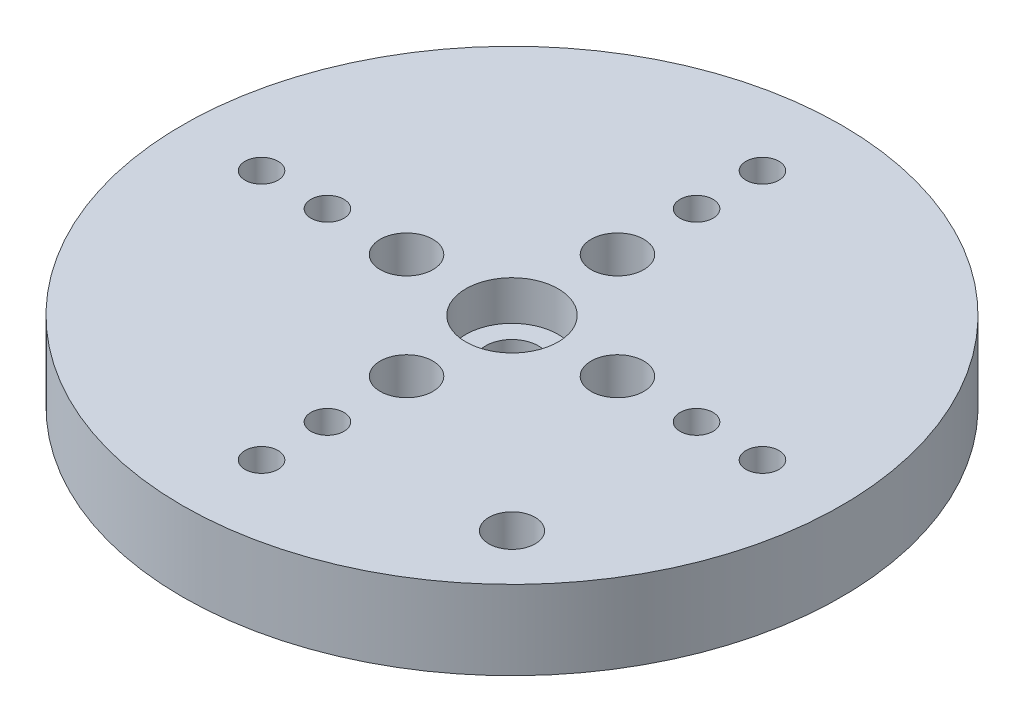
SolidWorks part; units mm, degrees
ref_plane "Front Plane" through (0, 0, 0) normal (0, 0, 1) x (1, 0, 0)
ref_plane "Top Plane" through (0, 0, 0) normal (0, 1, 0) x (1, 0, 0)
ref_plane "Right Plane" through (0, 0, 0) normal (1, 0, 0) x (0, 0, -1)
sketch "Sketch1" plane through (0, 0, 0) normal (0, 1, 0) x (1, 0, 0)
  circle A0 centre (0, 0) radius 25
  dimension "D1" = 50
extrude "Boss-Extrude1" add sketch "Sketch1" along normal blind 6
sketch "Sketch2" plane through (0, 6, 0) normal (0, 1, 0) x (1, 0, 0)
  line L0 (0, 0) -> (0, -19) construction
  circle A0 centre (0, -8) radius 2
  circle A1 centre (0, -14) radius 1.25
  circle A2 centre (0, -19) radius 1.25
  dimension "D1" = 4
  dimension "D2" = 2.5
  dimension "D3" = 2.5
  dimension "D4" = 19
  dimension "D5" = 14
  dimension "D6" = 8
extrude "Cut-Extrude1" cut sketch "Sketch2" against normal up to next
pattern_circular "CirPattern1" count 4 over 360 about axis through (0, 6, 0) along (0, -1, 0) of "Cut-Extrude1" reverse direction yes
sketch "Sketch3" plane through (0, 6, 0) normal (0, 1, 0) x (1, 0, 0)
  line L0 (0, 0) -> (14.1421, -14.1421) construction
  line L1 (0, 0) -> (0, -25) construction
  circle A0 centre (0, 0) radius 2
  circle A1 centre (14.1421, -14.1421) radius 1.75
  circle A2 centre (0, 0) radius 25 construction
  dimension "D2" = 3.5
  dimension "D4" = 4
  dimension "D1" = 20
  dimension "D3" = 45
extrude "Cut-Extrude2" cut sketch "Sketch3" against normal up to next
sketch "Sketch4" plane through (0, 6, 0) normal (0, 1, 0) x (1, 0, 0)
  circle A0 centre (0, 0) radius 3.5
  dimension "D1" = 7
extrude "Cut-Extrude3" cut sketch "Sketch4" against normal blind 3
